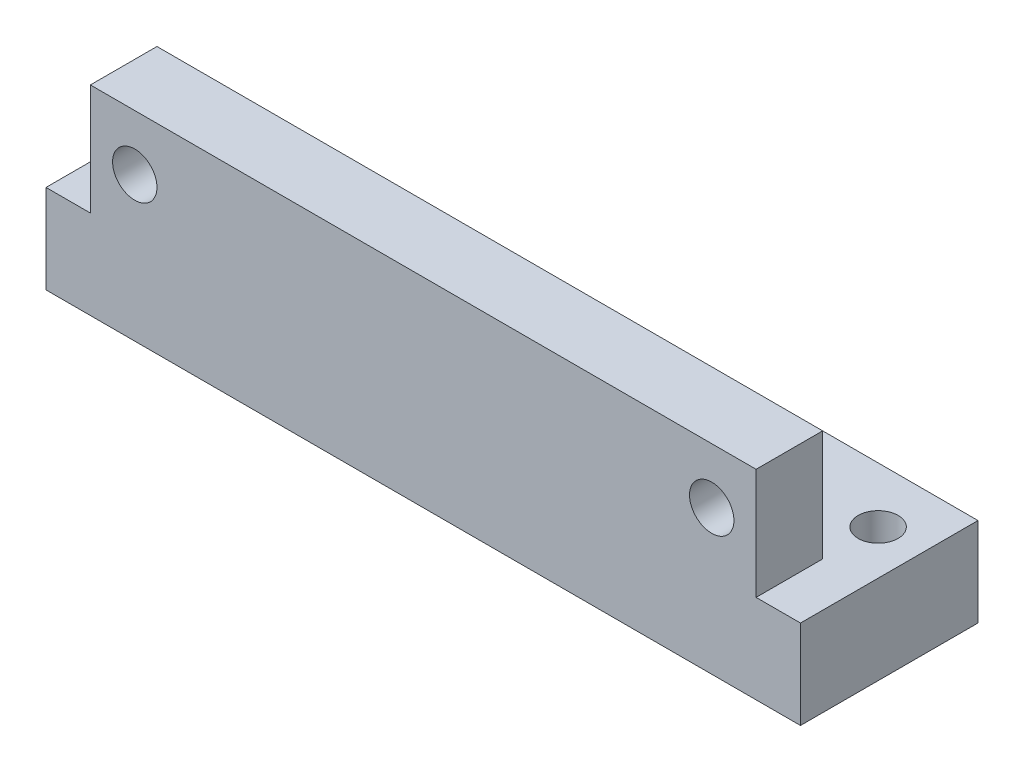
SolidWorks part; units mm, degrees
ref_plane "Front Plane" through (0, 0, 0) normal (0, 0, 1) x (1, 0, 0)
ref_plane "Top Plane" through (0, 0, 0) normal (0, 1, 0) x (1, 0, 0)
ref_plane "Right Plane" through (0, 0, 0) normal (1, 0, 0) x (0, 0, -1)
sketch "Sketch2" plane through (0, 0, 0) normal (0, 1, 0) x (1, 0, 0)
  line L1 (-21.59, -5.08) -> (21.59, -5.08)
  line L2 (-21.59, -5.08) -> (-21.59, 5.08)
  line L3 (-21.59, 5.08) -> (21.59, 5.08)
  line L4 (21.59, -5.08) -> (21.59, 5.08)
  line L5 (-21.59, -5.08) -> (21.59, 5.08) construction
  line L6 (-21.59, 5.08) -> (21.59, -5.08) construction
  point P0 (0, 0)
  dimension "D1" = 10.16
  dimension "D2" = 43.18
extrude "Boss-Extrude1" add sketch "Sketch2" along normal blind 5.08
sketch "Sketch3" plane through (0, 5.08, 0) normal (0, 1, 0) x (1, 0, 0)
  line L0 (0, -5.08) -> (0, 5.08) construction
  line L1 (-21.59, -5.08) -> (21.59, -5.08) construction
  line L2 (21.59, 5.08) -> (-21.59, 5.08) construction
  line L3 (-21.59, 5.08) -> (-21.59, -5.08) construction
  line L4 (-19.05, -5.08) -> (19.05, -5.08)
  line L5 (-19.05, -5.08) -> (-19.05, -1.27)
  line L6 (-19.05, -1.27) -> (19.05, -1.27)
  line L7 (19.05, -5.08) -> (19.05, -1.27)
  dimension "D1" = 38.1
  dimension "D2" = 2.54
  dimension "D3" = 3.81
extrude "Boss-Extrude2" add sketch "Sketch3" along normal blind 6.35
sketch "Sketch4" plane through (0, 5.08, 0) normal (0, 1, 0) x (1, 0, 0)
  line L0 (0, 5.08) -> (0, -1.27) construction
  line L1 (21.59, 5.08) -> (-21.59, 5.08) construction
  line L2 (19.05, -1.27) -> (-19.05, -1.27) construction
  line L3 (21.59, 1.905) -> (-21.59, 1.905) construction
  line L4 (-21.59, 5.08) -> (-21.59, -5.08) construction
  circle A0 centre (19.05, 1.905) radius 1.143
  circle A1 centre (-19.05, 1.905) radius 1.143
  point P11 (0, 1.905)
  dimension "D1" = 2.286
  dimension "D2" = 2.286
  dimension "D3" = 19.05
  dimension "D4" = 19.05
extrude "Cut-Extrude1" cut sketch "Sketch4" against normal through all
sketch "Sketch5" plane through (0, 0, 5.08) normal (0, 0, 1) x (1, 0, 0)
  line L0 (0, 11.43) -> (0, 0) construction
  line L1 (-19.05, 11.43) -> (19.05, 11.43) construction
  line L2 (-21.59, 0) -> (21.59, 0) construction
  line L3 (-19.05, 5.08) -> (19.05, 5.08) construction
  line L4 (19.05, 5.08) -> (19.05, 8.255) construction
  line L5 (19.05, 11.43) -> (19.05, 5.08) construction
  line L6 (19.05, 8.255) -> (-19.05, 8.255) construction
  line L7 (-19.05, 11.43) -> (-19.05, 5.08) construction
  circle A0 centre (-16.51, 8.255) radius 1.27
  circle A1 centre (16.51, 8.255) radius 1.27
  dimension "D1" = 2.54
  dimension "D2" = 33.02
extrude "Cut-Extrude2" cut sketch "Sketch5" against normal through all
